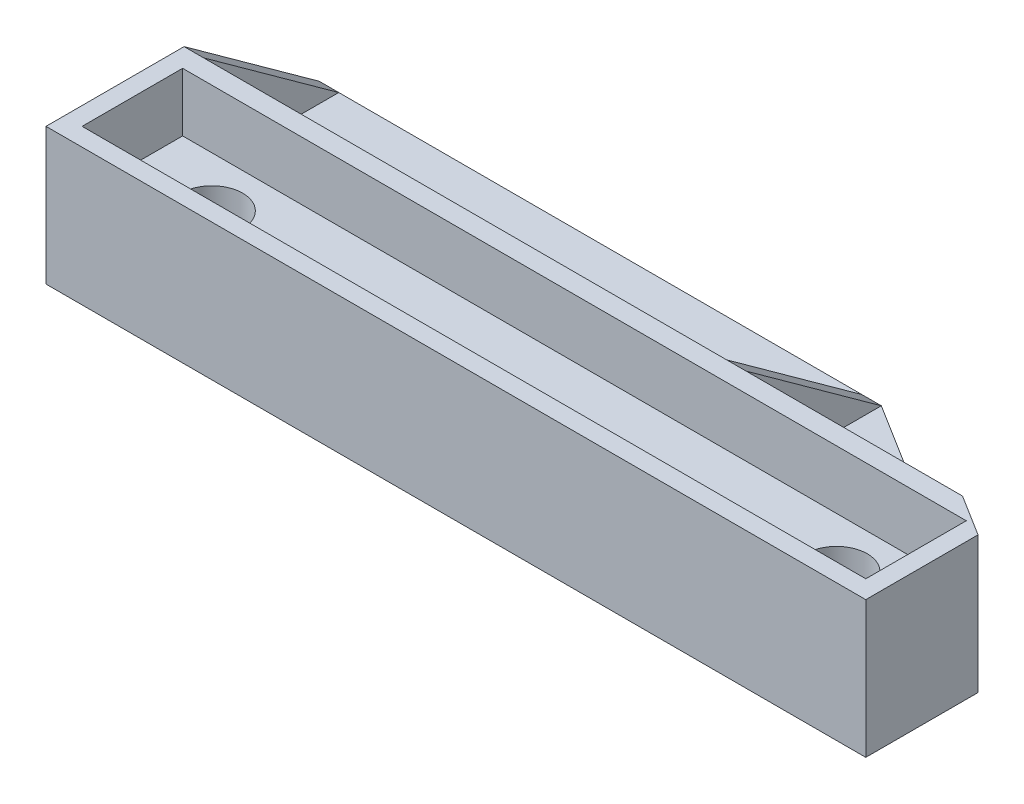
SolidWorks part; units mm, degrees
ref_plane "Front Plane" through (0, 0, 0) normal (0, 0, 1) x (1, 0, 0)
ref_plane "Top Plane" through (0, 0, 0) normal (0, 1, 0) x (1, 0, 0)
ref_plane "Right Plane" through (0, 0, 0) normal (1, 0, 0) x (0, 0, -1)
sketch "Sketch1" plane through (0, 0, 0) normal (0, 1, 0) x (1, 0, 0)
  line L0 (39.9996, 7) -> (42, 5.75)
  line L1 (0, 7) -> (39.9996, 7)
  line L2 (0, 7) -> (0, 0)
  line L3 (0, 0) -> (42, 0)
  line L4 (42, 5.75) -> (42, 0)
  dimension "D1" = 32
  dimension "D2" = 42
  dimension "D3" = 7
  dimension "D4" = 5.75
extrude "Riser" add sketch "Sketch1" along normal blind 7
sketch "Sketch2" plane through (0, 0, 0) normal (0, -1, 0) x (1, 0, 0)
  line L0 (0, -7) -> (0, 0) construction
  line L1 (21, 0) -> (21, -7) construction
  line L2 (0, 0) -> (42, 0) construction
  line L4 (39.9996, -7) -> (0, -7) construction
  circle A2 centre (5, -3.5) radius 1.575
  circle A3 centre (37, -3.5) radius 1.575
  point P2 (0, -3.5)
  dimension "D2" = 3.15
  dimension "D1" = 5
extrude "Mounting Holes" cut sketch "Sketch2" against normal through all
sketch "Sketch3" plane through (0, 7, 0) normal (0, 1, 0) x (1, 0, 0)
  line L12 (0.925, 6.075) -> (41.075, 6.075)
  line L13 (0.925, 6.075) -> (0.925, 0.925)
  line L14 (0.925, 0.925) -> (41.075, 0.925)
  line L15 (41.075, 6.075) -> (41.075, 0.925)
  line L17 (0, 7) -> (0, 0) construction
  line L18 (39.9996, 7) -> (0, 7) construction
  dimension "D1" = 5.15
  dimension "D2" = 40.15
  dimension "D3" = 0.925
  dimension "D4" = 0.925
extrude "Recess" cut sketch "Sketch3" against normal blind 3 contours L12 L15 L14 L13
sketch "Sketch4" plane through (0, 0, 0) normal (0, 1, 0) x (1, 0, 0)
  line L0 (16.7153, 21.5496) -> (46.0747, 3.2038) construction
  line L1 (0, 7) -> (39.9996, 7)
  line L2 (39.9996, 7) -> (28.7972, 14)
  line L3 (28.7972, 14) -> (0, 14)
  line L4 (0, 14) -> (0, 7)
  line L5 (42, 5.75) -> (39.9996, 7) construction
  dimension "D1" = 7
extrude "Flange" add sketch "Sketch4" along normal blind 7
sketch "Sketch5" plane through (0, 7, 0) normal (0, 1, 0) x (1, 0, 0)
  line L0 (1, 7.075) -> (1, 14)
  line L1 (28.7972, 14) -> (0, 14) construction
  line L2 (1, 14) -> (27.7972, 14)
  line L3 (27.7972, 14) -> (27.7972, 7.075)
  line L4 (27.7972, 7.075) -> (1, 7.075)
  line L11 (0, 14) -> (0, 0) construction
  line L12 (0.925, 6.075) -> (41.075, 6.075) construction
  line L13 (28.7972, 14) -> (28.7972, 7.075)
  line L14 (28.7972, 7.075) -> (39.8796, 7.075)
  line L15 (42, 5.75) -> (28.7972, 14) construction
  line L16 (39.8796, 7.075) -> (28.7972, 14)
  dimension "D1" = 1
  dimension "D2" = 1
  dimension "D3" = 1
extrude "Flange Cutout" cut sketch "Sketch5" against normal blind 5
sketch "Sketch7" plane through (27.7972, 0, 0) normal (-1, 0, 0) x (0, 0, 1)
  line L0 (-7.075, 7) -> (-14, 2)
  line L1 (-14, 2) -> (-14, 7)
  line L2 (-14, 7) -> (-7.075, 7)
extrude "Angle Cutout" cut sketch "Sketch7" against normal through all and the other way through all
chamfer "Flange Chamfer 1" distance 1 angle 45 1 edges at (14.3986, 2, -7.075)
chamfer "Flange Chamfer 2" distance 1 angle 45 1 edges at (34.3384, 2, -7.075)
